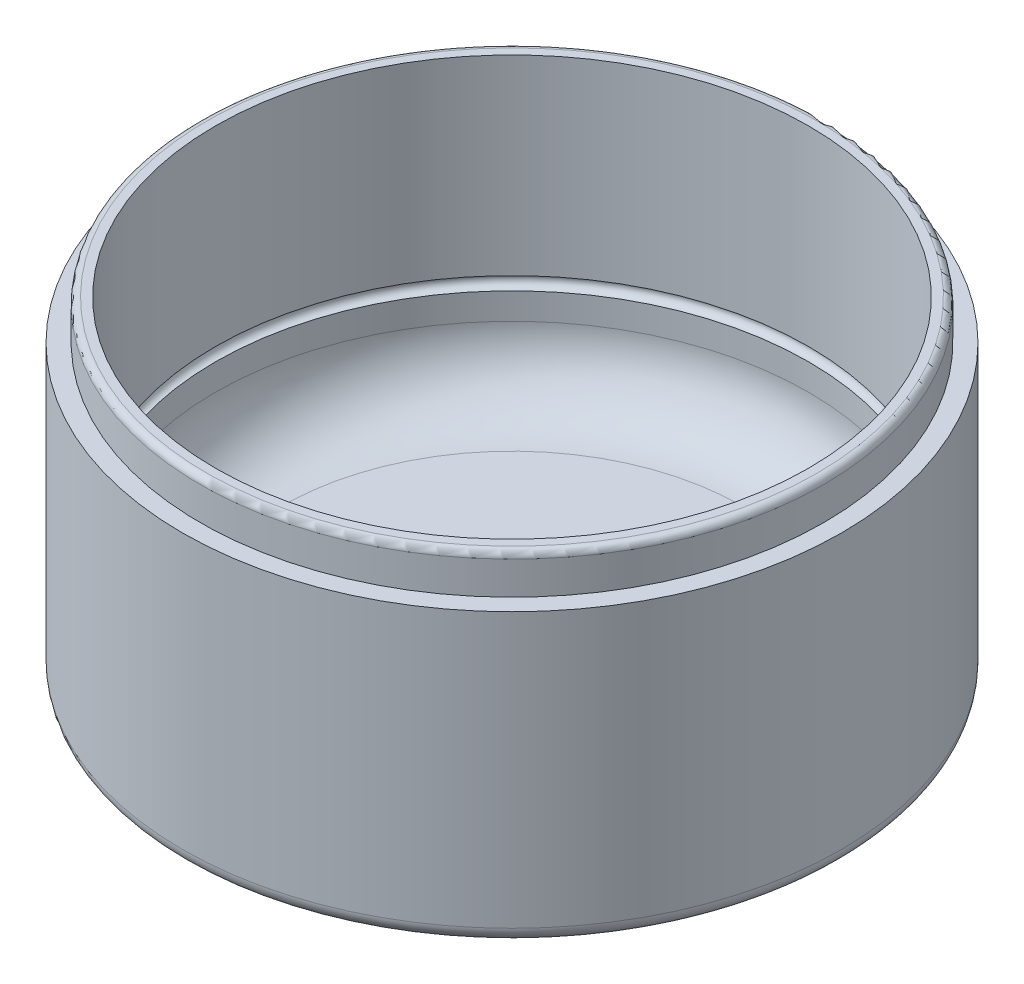
SolidWorks part; units mm, degrees
ref_plane "Front (XY)" through (0, 0, 0) normal (0, 0, 1) x (1, 0, 0)
ref_plane "Top (XZ)" through (0, 0, 0) normal (0, 1, 0) x (1, 0, 0)
ref_plane "Right (YZ)" through (0, 0, 0) normal (1, 0, 0) x (0, 0, -1)
sketch "Sketch1" plane through (0, 0, 0) normal (0, 1, 0) x (1, 0, 0)
  circle A0 centre (0, 0) radius 50
  dimension "D1" = 100
extrude "Boss-Extrude1" add sketch "Sketch1" against normal blind 50
shell "Shell2" thickness 5 removed face at (0, 0, 50)
sketch "Sketch2" plane through (0, 0, 0) normal (0, 1, 0) x (1, 0, 0)
  line L0 (0, 0) -> (50, 0) construction
  circle A2 centre (0, 0) radius 50 construction
sketch "Sketch3" plane through (0, 0, 0) normal (0, 0, 1) x (1, 0, 0)
  line L0 (50, 0) -> (47.3, 0)
  line L1 (0, 0) -> (50, 0) construction
  line L2 (47.3, 0) -> (47.3, -6)
  line L3 (47.3, -6) -> (50, -6)
  line L4 (50, -50) -> (50, 0) construction
  line L5 (50, -6) -> (50, 0)
  dimension "D1" = 6
  dimension "D2" = 2.7
sketch "Sketch4" plane through (0, 0, 0) normal (0, 1, 0) x (1, 0, 0)
  circle A2 centre (0, 0) radius 47.6
  circle A3 centre (0, 0) radius 47.6
  dimension "D1" = 2.4
sweep "Cut-Sweep1" cut profiles "Sketch3" path "Sketch4"
fillet "Fillet1" radius 1 1 edges at (47.3, 0, 0)
fillet "Fillet2" radius 10 1 edges at (0, -45, 45)
fillet "Fillet3" radius 2.4 1 edges at (0, -50, 50)
ref_plane "Plane1" through (0, -30, 0) normal (0, 1, 0) x (1, 0, 0)
sketch "Sketch5" plane through (0, -30, 0) normal (0, 1, 0) x (1, 0, 0)
  circle A0 centre (0, 0) radius 45
sketch "Sketch6" plane through (0, 0, 0) normal (0, 0, 1) x (1, 0, 0)
  line L0 (0, -30) -> (45, -30) construction
  line L1 (45, -30) -> (-45, -30) construction
  circle A0 centre (45, -30) radius 1
  dimension "D1" = 2
sweep "Cut-Sweep2" cut profiles "Sketch6" path "Sketch5"
